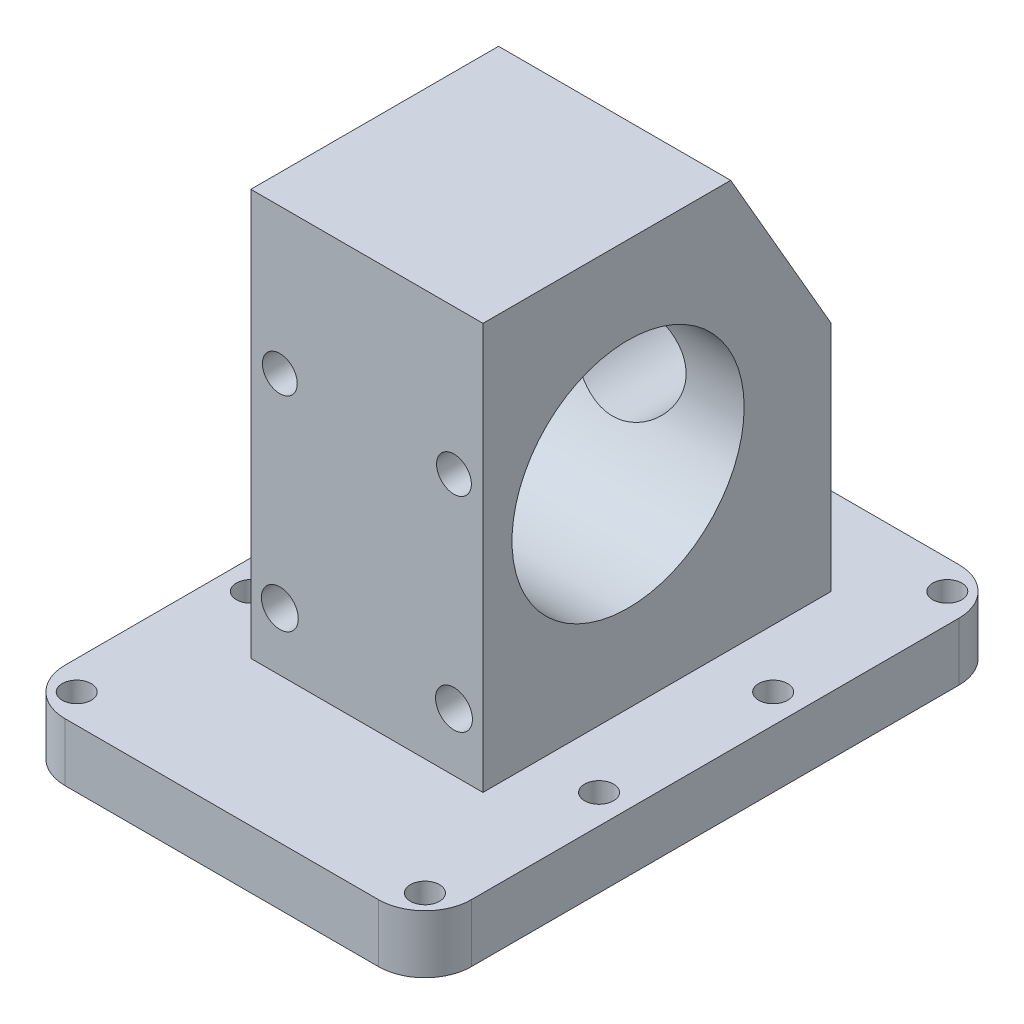
SolidWorks part; units mm, degrees
material "Brass"
ref_plane "Front Plane" through (0, 0, 0) normal (0, 0, 1) x (1, 0, 0)
ref_plane "Top Plane" through (0, 0, 0) normal (0, 1, 0) x (1, 0, 0)
ref_plane "Right Plane" through (0, 0, 0) normal (1, 0, 0) x (0, 0, -1)
sketch "Sketch1" plane through (0, 0, 0) normal (1, 0, 0) x (0, 0, -1)
  line L1 (-25, 35) -> (35, 35)
  line L2 (-25, 35) -> (-25, -35)
  line L3 (-25, -35) -> (35, -35)
  line L4 (35, 35) -> (35, -35)
  point P0 (0, 0)
  point P6 (0, 0)
  dimension "D3" = 60
  dimension "D8" = 70
extrude "BODY" add sketch "Sketch1" along normal mid plane 40
sketch "Sketch17" plane through (20, 0, 0) normal (1, 0, 0) x (0, 0, -1)
  circle A0 centre (0, 0) radius 20
  dimension "D1" = 40
extrude "Big Hole" cut sketch "Sketch17" against normal through all
sketch "Sketch7" plane through (0, -35, 0) normal (0, -1, 0) x (1, 0, 0)
  line L0 (22, 0) -> (-22, 0) construction
  line L1 (35, 50) -> (-35, 50)
  line L2 (35, 50) -> (35, -50)
  line L3 (35, -50) -> (-35, -50)
  line L4 (-35, 50) -> (-35, -50)
  line L5 (35, 50) -> (-35, -50) construction
  line L6 (35, -50) -> (-35, 50) construction
  point P0 (0, 0)
  dimension "D2" = 70
  dimension "D3" = 100
extrude "BASE" add sketch "Sketch7" along normal blind 10
sketch "Sketch18" plane through (20, 0, 0) normal (1, 0, 0) x (0, 0, -1)
  line L0 (17.6795, 35) -> (35, 5)
  line L1 (35, 35) -> (-25, 35) construction
  line L2 (35, -35) -> (35, 35) construction
  line L3 (35, 5) -> (35, 35)
  line L4 (35, 35) -> (17.6795, 35)
  line L5 (50, -45) -> (-50, -45) construction
  dimension "D1" = 50
  dimension "D2" = 30
extrude "Cut-Extrude1_Slope_RIGHT" cut sketch "Sketch18" against normal through all
sketch "Sketch12" plane through (0, 0, -35) normal (0, 0, -1) x (-1, 0, 0)
  circle A0 centre (0, 0) radius 10.005
  dimension "D1" = 20.01
extrude "Cut-Extrude hole RIGHT" cut sketch "Sketch12" against normal up to next
hole_wizard "Ø6.0 (6) Diameter Hole1" positions "Sketch6" profile "Sketch5" hole size "Ø6.0" standard "ANSI Metric" end condition up to next
sketch "Sketch6" plane through (0, 0, 25) normal (0, 0, 1) x (1, 0, 0)
  line L2 (20, 35) -> (20, -35) construction
  line L3 (35, -45) -> (-35, -45) construction
  point P0 (15, 10)
  dimension "D1" = 5
  dimension "D2" = 55
sketch "Sketch5" plane through (15, 10, 25) normal (1, 0, 0) x (0, -1, 0)
  line L0 (0, 0) -> (0, 7.6795)
  line L1 (0, 7.6795) -> (3, 7.6795)
  line L2 (3, 7.6795) -> (3, 0)
  line L5 (3, 0) -> (0, 0)
  line L11 (0, -6.35) -> (0, 107.95) construction
  dimension "Thru Hole Dia." = 6
  dimension "Thru Hole Depth" = 7.6795
mirror "Mirror1" about plane through (0, 0, 0) normal (1, 0, 0) of "Ø6.0 (6) Diameter Hole1"
hole_wizard "1/4 (0.25) Diameter Hole1" positions "Sketch13" profile "Sketch14" hole size "1/4" standard "ANSI Inch" end condition through all
sketch "Sketch13" plane through (0, 0, 25) normal (0, 0, 1) x (1, 0, 0)
  line L0 (20, 35) -> (20, -35) construction
  line L1 (35, -45) -> (-35, -45) construction
  point P0 (15, -25)
  dimension "D1" = 5
  dimension "D2" = 20
sketch "Sketch14" plane through (15, -25, 25) normal (1, 0, 0) x (0, -1, 0)
  line L0 (0, 0) -> (0, 75)
  line L1 (0, 75) -> (3.175, 75)
  line L2 (3.175, 75) -> (3.175, 0)
  line L5 (3.175, 0) -> (0, 0)
  line L11 (0, -6.35) -> (0, 107.95) construction
  dimension "Thru Hole Dia." = 6.35
  dimension "Thru Hole Depth" = 75
mirror "Mirror2" about plane through (0, 0, 0) normal (1, 0, 0) of "1/4 (0.25) Diameter Hole1"
hole_wizard "Ø5.0 (5) Diameter Hole1" positions "Sketch9" profile "Sketch10" hole size "Ø5.0" standard "ANSI Metric" end condition through all
sketch "Sketch9" plane through (0, -35, 0) normal (0, 1, 0) x (-1, 0, 0)
  line L0 (35, 50) -> (35, -50) construction
  line L1 (-35, 50) -> (35, 50) construction
  point P0 (30, 45)
  dimension "D1" = 5
  dimension "D2" = 5
sketch "Sketch10" plane through (-30, -35, 45) normal (1, 0, 0) x (0, 0, 1)
  line L0 (0, 0) -> (0, 10)
  line L1 (0, 10) -> (2.5, 10)
  line L2 (2.5, 10) -> (2.5, 0)
  line L5 (2.5, 0) -> (0, 0)
  line L11 (0, -6.35) -> (0, 107.95) construction
  dimension "Thru Hole Dia." = 5
  dimension "Thru Hole Depth" = 10
pattern_linear "LPattern5" count 3 spacing 30 along (0, 0, -1) count 2 spacing 60 along (1, 0, 0) of "Ø5.0 (5) Diameter Hole1"
hole_wizard "M6x1.0 Tapped Hole1" positions "Sketch15" profile "Sketch16" tap size "M6x1.0" standard "ANSI Metric" end condition through all
sketch "Sketch15" plane through (0, -35, 0) normal (0, 1, 0) x (1, 0, 0)
  line L0 (-35, 50) -> (35, 50) construction
  line L1 (35, 50) -> (35, -50) construction
  point P0 (-30, 45)
  point P2 (30, 45)
  dimension "D1" = 5
  dimension "D2" = 5
  dimension "D3" = 60
  dimension "D4" = 5
sketch "Sketch16" plane through (-30, -35, -45) normal (1, 0, 0) x (0, 0, 1)
  line L0 (0, 0) -> (0, 10)
  line L1 (0, 10) -> (2.5, 10)
  line L2 (2.5, 10) -> (2.5, 0)
  line L5 (2.5, 0) -> (0, 0)
  line L11 (0, -6.35) -> (0, 107.95) construction
  dimension "Thru Tap Drill Dia." = 5
  dimension "Thru Tap Drill Depth" = 10
cosmetic thread "Hole Thread1" parameters "D2"=6
cosmetic thread "Hole Thread2" parameters "D2"=6
fillet "Fillet1" radius 8 4 edges at (-35, -40, -50) (35, -40, -50) (35, -40, 50) (-35, -40, 50)
hole_wizard "M3x0.5 Tapped Hole1" positions "Sketch19" profile "Sketch20" tap size "M3x0.5" standard "ANSI Metric"
sketch "Sketch19" plane through (0, 16.4054, -28.4151) normal (0, 0.5, -0.866) x (-1, 0, 0)
  line L0 (-8.666, -13.1699) -> (-20, -13.1699) construction
  line L1 (-20, 21.4711) -> (-20, -13.1699) construction
  point P0 (-15, -3.1699)
  dimension "D1" = 10
  dimension "D2" = 5
sketch "Sketch20" plane through (15, 13.6603, -30) normal (1, 0, 0) x (0, 0.866, 0.5)
  line L0 (0, 0) -> (0, 8.2511)
  line L1 (0, 8.2511) -> (1.25, 7.5)
  line L2 (1.25, 7.5) -> (1.25, 0)
  line L5 (1.25, 0) -> (0, 0)
  line L10 (0, 8.2511) -> (-1.25, 7.5) construction
  line L11 (0, -6.35) -> (0, 107.95) construction
  dimension "Tap Drill Dia." = 2.5
  dimension "Tap Drill Depth" = 7.5
  dimension "Drill Angle" = 118
cosmetic thread "Hole Thread4" parameters "D1"=6, "D2"=3.5
pattern_linear "LPattern6" count 4 spacing 10 along (-1, 0, 0) count 3 spacing 6 along (0, 0.866, 0.5) of "M3x0.5 Tapped Hole1"
